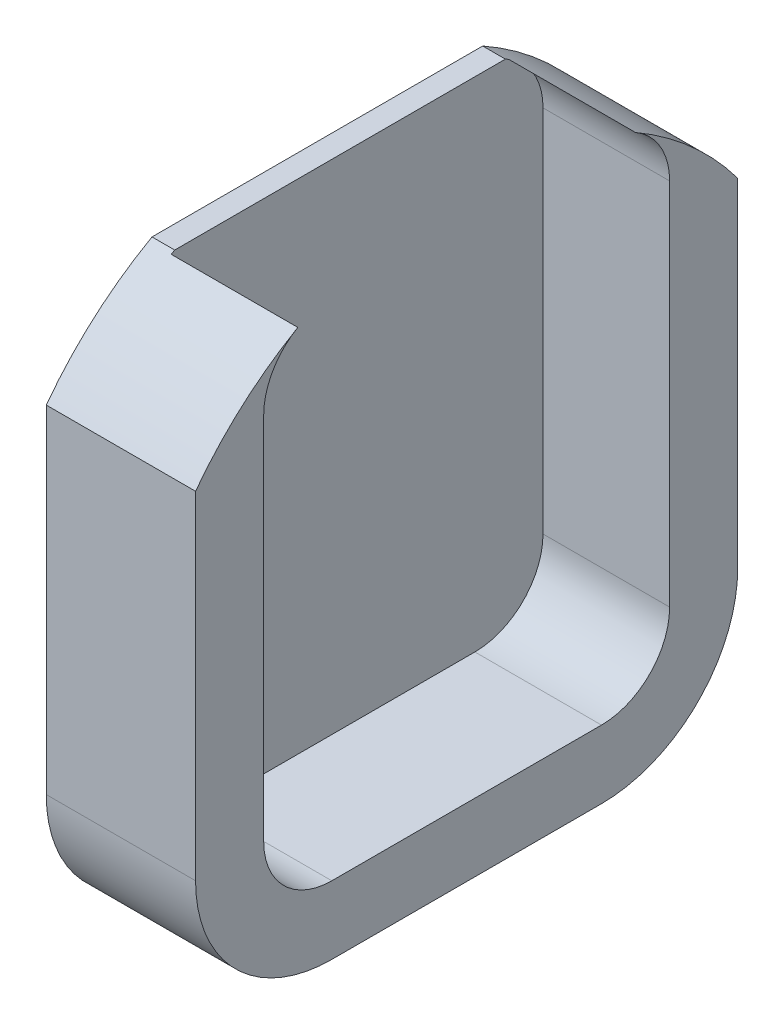
SolidWorks part; units mm, degrees
note: The reader was unsure of these and kept them because the rebuilt part matched: shared geometry of "Sketch2<3>".
material "ABS"
ref_plane "Front Plane" through (0, 0, 0) normal (0, 0, 1) x (1, 0, 0)
ref_plane "Top Plane" through (0, 0, 0) normal (0, 1, 0) x (1, 0, 0)
ref_plane "Right Plane" through (0, 0, 0) normal (1, 0, 0) x (0, 0, -1)
sketch "Sketch2" plane through (0, 0, 0) normal (1, 0, 0) x (0, 0, -1)
  line L0 (17, 6) -> (17, 6.8745) construction
  line L1 (-17, 6.8745) -> (-17, 6) construction
  line L2 (-17, 6) -> (17, 6) construction
  line L3 (23.875, 1.0053) -> (23.875, -31.875) construction
  line L4 (11.875, -43.875) -> (-11.875, -43.875) construction
  line L5 (-23.875, -31.875) -> (-23.875, 1.0053) construction
  line L6 (17.875, 0.6258) -> (17.875, -31.875) construction
  line L7 (11.875, -37.875) -> (-11.875, -37.875) construction
  line L8 (-17.875, -31.875) -> (-17.875, 0.6258) construction
  line L9 (17, 6) -> (17, 6.8745)
  line L10 (-17, 6.8745) -> (-17, 6)
  line L11 (-17, 6) -> (17, 6)
  line L12 (23.875, 1.0053) -> (23.875, -31.875)
  line L13 (11.875, -43.875) -> (-11.875, -43.875)
  line L14 (-23.875, -31.875) -> (-23.875, 1.0053)
  line L15 (17.875, 0.6258) -> (17.875, -31.875)
  line L16 (11.875, -37.875) -> (-11.875, -37.875)
  line L17 (-17.875, -31.875) -> (-17.875, 0.6258)
  arc A0 (11.875, -43.875) -> (23.875, -31.875) centre (11.875, -31.875) ccw construction
  arc A1 (-23.875, -31.875) -> (-11.875, -43.875) centre (-11.875, -31.875) ccw construction
  arc A2 (23.875, 1.0053) -> (-23.875, 1.0053) centre (0, -20) ccw construction
  arc A3 (11.875, -37.875) -> (17.875, -31.875) centre (11.875, -31.875) ccw construction
  arc A4 (-17.875, -31.875) -> (-11.875, -37.875) centre (-11.875, -31.875) ccw construction
  arc A5 (-14.8687, 5.8256) -> (-17.875, 0.6258) centre (-11.875, 0.6258) ccw construction
  arc A6 (14.8687, 5.8256) -> (-14.8687, 5.8256) centre (0, -20) ccw construction
  arc A7 (17.875, 0.6258) -> (14.8687, 5.8256) centre (11.875, 0.6258) ccw construction
  arc A8 (11.875, -43.875) -> (23.875, -31.875) centre (11.875, -31.875) ccw
  arc A9 (-23.875, -31.875) -> (-11.875, -43.875) centre (-11.875, -31.875) ccw
  arc A10 (23.875, 1.0053) -> (-23.875, 1.0053) centre (0, -20) ccw
  arc A11 (11.875, -37.875) -> (17.875, -31.875) centre (11.875, -31.875) ccw
  arc A12 (-17.875, -31.875) -> (-11.875, -37.875) centre (-11.875, -31.875) ccw
  arc A13 (-14.8687, 5.8256) -> (-17.875, 0.6258) centre (-11.875, 0.6258) ccw
  arc A14 (14.8687, 5.8256) -> (17, 4.4753) centre (0, -20) ccw
  arc A15 (17.875, 0.6258) -> (14.8687, 5.8256) centre (11.875, 0.6258) ccw
  arc A16 (-17, 4.4753) -> (-14.8687, 5.8256) centre (0, -20) ccw
extrude "Boss-Extrude1" add sketch "Sketch2" along normal up to vertex from vertex contours A16 L10 A10 L14 A9 L13 A8 L12 L9 A14 A15 L15 A11 L16 A12 L17 A13 | L10 A16 A13 L17 A12 L16 A11 L15 A15 A14 L9 L11
extrude "Boss-Extrude2" add sketch "Sketch2<3>" against normal up to vertex (11.15 mm away) contours A16 L10 A10 L14 A9 L13 A8 L12 L9 A14 A15 L15 A11 L16 A12 L17 A13
sketch "Sketch2<3>" plane through (0, 0, 0) normal (1, 0, 0) x (0, 0, -1) same geometry as "Sketch2"
